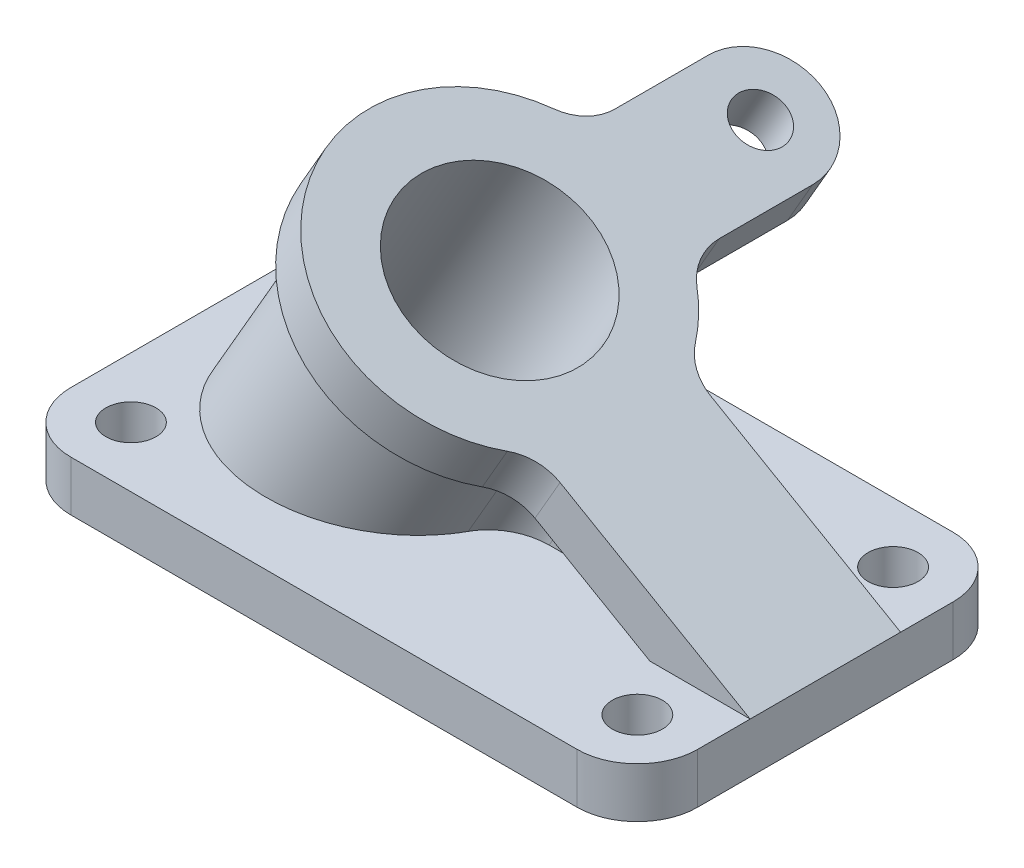
SolidWorks part; units mm, degrees
ref_plane "前视基准面" through (0, 0, 0) normal (0, 0, 1) x (1, 0, 0)
ref_plane "上视基准面" through (0, 0, 0) normal (0, 1, 0) x (1, 0, 0)
ref_plane "右视基准面" through (0, 0, 0) normal (1, 0, 0) x (0, 0, -1)
other "Configuration Table"
sketch "草图7" plane through (0, 0, 0) normal (0, 1, 0) x (1, 0, 0)
  line L0 (-38.5, 25.5) -> (38.5, 25.5)
  line L1 (-50.5, 37.5) -> (50.5, 37.5)
  line L2 (-62.5, 25.5) -> (-62.5, -25.5)
  line L3 (-50.5, -37.5) -> (50.5, -37.5)
  line L4 (62.5, 25.5) -> (62.5, -25.5)
  line L5 (-62.5, 37.5) -> (62.5, -37.5) construction
  line L6 (-62.5, -37.5) -> (62.5, 37.5) construction
  line L7 (50.5, 13.5) -> (50.5, -13.5)
  line L8 (-38.5, -25.5) -> (38.5, -25.5)
  line L9 (-50.5, 13.5) -> (-50.5, -13.5)
  line L10 (-50.5, 25.5) -> (50.5, 25.5) construction
  line L11 (50.5, 25.5) -> (50.5, -25.5) construction
  line L12 (-50.5, 25.5) -> (-50.5, -25.5) construction
  line L13 (-50.5, -25.5) -> (50.5, -25.5) construction
  arc A0 (50.5, 37.5) -> (62.5, 25.5) centre (50.5, 25.5) cw
  arc A1 (-62.5, -25.5) -> (-50.5, -37.5) centre (-50.5, -25.5) ccw
  arc A2 (-50.5, 37.5) -> (-62.5, 25.5) centre (-50.5, 25.5) ccw
  arc A3 (50.5, -37.5) -> (62.5, -25.5) centre (50.5, -25.5) ccw
  arc A4 (50.5, 25.5) -> (50.5, 25.5) centre (50.5, 25.5) cw
  arc A5 (50.5, -25.5) -> (50.5, -25.5) centre (50.5, -25.5) ccw
  arc A6 (-50.5, -25.5) -> (-50.5, -25.5) centre (-50.5, -25.5) ccw
  arc A7 (-50.5, 25.5) -> (-50.5, 25.5) centre (-50.5, 25.5) ccw
  arc A8 (-50.5, 13.5) -> (-38.5, 25.5) centre (-50.5, 25.5) ccw
  arc A9 (62.5, 25.5) -> (50.5, 37.5) centre (50.5, 25.5) ccw
  arc A10 (-38.5, -25.5) -> (-50.5, -13.5) centre (-50.5, -25.5) ccw
  arc A11 (50.5, -37.5) -> (62.5, -25.5) centre (50.5, -25.5) ccw
  arc A12 (-50.5, 37.5) -> (-62.5, 25.5) centre (-50.5, 25.5) ccw
  arc A13 (-62.5, -25.5) -> (-50.5, -37.5) centre (-50.5, -25.5) ccw
  arc A14 (50.5, -13.5) -> (38.5, -25.5) centre (50.5, -25.5) ccw
  arc A15 (38.5, 25.5) -> (50.5, 13.5) centre (50.5, 25.5) ccw
  circle A16 centre (-50.5, 25.5) radius 5
  circle A17 centre (50.5, 25.5) radius 5
  circle A18 centre (-50.5, -25.5) radius 5
  circle A19 centre (50.5, -25.5) radius 5
  point P0 (0, 0)
  dimension "D3" = 12
  dimension "D5" = 24
  dimension "D4" = 10
  dimension "D1" = 125
  dimension "D2" = 75
extrude "凸台-拉伸5" add sketch "草图7" along normal blind 10 contours A15 L0 A8 L9 A10 L8 A14 L7 | L3 A3 L4 A0 L1 A2 L2 A1 A19 A18 A17 A16 L0 A15 L7 A14 L8 A10 L9 A8 region at (0, 0, 0) region at (0, 0, -36.0423)
extrude "切除-拉伸3" cut sketch "草图7<3>" along normal blind 4 contours A15 L0 A8 L9 A10 L8 A14 L7 region at (0, 0, 0)
sketch "草图7<3>" plane through (0, 0, 0) normal (0, 1, 0) x (1, 0, 0) same geometry as "草图7"
ref_plane "基准面3" through (19.9551, 34.5633, 0) normal (0.5, 0.866, 0) x (0, 0, 1)
sketch "草图8" plane through (19.9551, 34.5633, 0) normal (0.5, 0.866, 0) x (0, 0, 1)
  line L0 (0, 49.1266) -> (0, -77.5357) construction
  line L1 (-25.5, 49.1266) -> (25.5, 49.1266) construction
  line L2 (-5, 49.1266) -> (-5, 5.7494)
  line L3 (-15, 49.1266) -> (-15, 5.3516)
  line L4 (-15, 49.1266) -> (15, 49.1266)
  line L5 (5, 49.1266) -> (5, 5.7494)
  line L6 (15, 49.1266) -> (15, 5.3516)
  line L7 (-52, -13.8734) -> (-33.4066, -13.8734)
  line L8 (-52, -37.8734) -> (-33.4066, -37.8734)
  line L9 (0, -25.8734) -> (-104, -25.8734) construction
  arc A0 (-25.0549, -42.3734) -> (18.75, -2.4547) centre (0, -25.8734) ccw
  arc A1 (-10.7143, -3.2857) -> (10.7143, -3.2857) centre (0, -25.8734) ccw
  circle A2 centre (0, -25.8734) radius 18
  arc A3 (-52, -13.8734) -> (-52, -37.8734) centre (-52, -25.8734) ccw
  circle A4 centre (-52, -25.8734) radius 5
  arc A5 (-18.75, -2.4547) -> (-25.0549, -9.3734) centre (0, -25.8734) ccw
  arc A6 (-5, 5.7494) -> (-10.7143, -3.2857) centre (-15, 5.7494) cw
  arc A7 (5, 5.7494) -> (10.7143, -3.2857) centre (15, 5.7494) ccw
  arc A8 (15, 5.3516) -> (18.75, -2.4547) centre (25, 5.3516) ccw
  arc A9 (-15, 5.3516) -> (-18.75, -2.4547) centre (-25, 5.3516) cw
  arc A10 (-33.4066, -37.8734) -> (-25.0549, -42.3734) centre (-33.4066, -47.8734) cw
  arc A11 (-33.4066, -13.8734) -> (-25.0549, -9.3734) centre (-33.4066, -3.8734) ccw
  point P9 (-15, 27.2391)
  point P25 (0, 0)
  point P30 (15, 0.1073)
  point P33 (-15, 0.1073)
  dimension "D3" = 36
  dimension "D4" = 60
  dimension "D5" = 50
  dimension "D7" = 24
  dimension "D8" = 10
  dimension "D10" = 10
  dimension "D1" = 10
  dimension "D2" = 30
  dimension "D6" = 75
  dimension "D9" = 52
extrude "凸台-拉伸8" add sketch "草图8" against normal blind 10 contours A11 L7 A3 L8 A10 A0 A8 L6 L4 L5 A7 A1 A6 L2 L3 A9 A5 A4 region at (43.7171, 20.8443, -6.4093)
extrude "凸台-拉伸9" add sketch "草图8<6>" against normal up to next contours A7 L5 L4 L2 A6 A1 A2 region at (61.5318, 10.559, 0)
sketch "草图8<6>" plane through (19.9551, 34.5633, 0) normal (0.5, 0.866, 0) x (0, 0, 1) same geometry as "草图8"
extrude "切除-拉伸5" cut sketch "草图8<7>" against normal up to next contours A2 region at (-2.4519, 47.5, 0)
sketch "草图8<7>" plane through (19.9551, 34.5633, 0) normal (0.5, 0.866, 0) x (0, 0, 1) same geometry as "草图8"
ref_plane "基准面5" through (-22.407, 12.9367, 0) normal (-0.866, 0.5, 0) x (0, 0, 1)
sketch "草图10" plane through (-22.407, 12.9367, 0) normal (-0.866, 0.5, 0) x (0, 0, 1)
  line L0 (-42, 29.9103) -> (-25, 2.9103)
  line L1 (-52, 29.9103) -> (-33.4066, 29.9103) construction
  line L2 (-25, 29.9103) -> (-25, -3.391) construction
  line L3 (-33.4066, 29.9103) -> (-25.0549, 29.9103) construction
  line L4 (-52, 29.9103) -> (-52, 39.9103) construction
  dimension "D1" = 27
  dimension "D2" = 10
rib "筋9" sketch "草图10" sketch "草图10" thickness 10 extrusion direction parallel to sketch draft on no parameters "D1"=10
